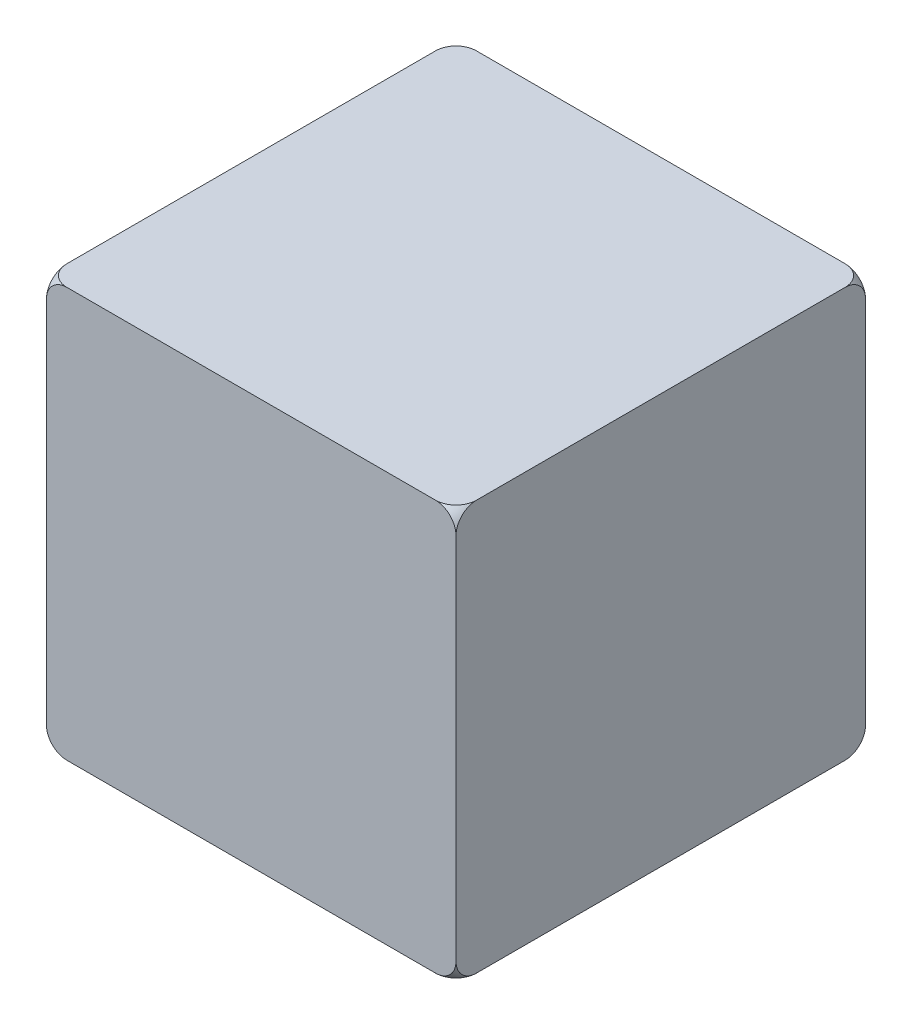
SolidWorks part; units mm, degrees
ref_plane "Plano frontal" through (0, 0, 0) normal (0, 0, 1) x (1, 0, 0)
ref_plane "Plano superior" through (0, 0, 0) normal (0, 1, 0) x (1, 0, 0)
ref_plane "Plano direito" through (0, 0, 0) normal (1, 0, 0) x (0, 0, -1)
sketch3d "3DSketch1"
  line L0 (0, 0, 0) -> (0.5, 0, 0) construction
  line L1 (0.5, 0, 0) -> (9.5, 0, 0) construction
  line L2 (9.5, 0, 0) -> (10, 0, 0) construction
  line L3 (10, 0, 0) -> (10, 0.5, 0) construction
  line L4 (10, 0.5, 0) -> (10, 9.5, 0) construction
  line L5 (10, 10, 0) -> (9.5, 10, 0) construction
  line L6 (9.5, 10, 0) -> (0.5, 10, 0) construction
  line L7 (0.5, 10, 0) -> (0, 10, 0) construction
  line L8 (0, 10, 0) -> (0, 9.5, 0) construction
  line L9 (0, 9.5, 0) -> (0, 0.5, 0) construction
  line L10 (0, 0.5, 0) -> (0, 0, 0) construction
  line L11 (10, 9.5, 0) -> (10, 10, 0) construction
  line L12 (0, 0, 0) -> (0, 0, 0.5) construction
  line L13 (0, 0, 0.5) -> (0, 0, 9.5) construction
  line L14 (0, 0, 9.5) -> (0, 0, 10) construction
  line L15 (0, 0, 10) -> (0, 0.5, 10) construction
  line L16 (0, 0.5, 10) -> (0, 9.5, 10) construction
  line L17 (0, 9.5, 10) -> (0, 10, 10) construction
  line L18 (0, 10, 0) -> (0, 10, 0.5) construction
  line L19 (0, 10, 0.5) -> (0, 10, 9.5) construction
  line L20 (0, 10, 9.5) -> (0, 10, 10) construction
  line L21 (0, 0, 10) -> (0.5, 0, 10) construction
  line L22 (0.5, 0, 10) -> (9.5, 0, 10) construction
  line L23 (9.5, 0, 10) -> (10, 0, 10) construction
  line L24 (10, 0, 0) -> (10, 0, 0.5) construction
  line L25 (10, 0, 0.5) -> (10, 0, 9.5) construction
  line L26 (10, 0, 9.5) -> (10, 0, 10) construction
  line L27 (10, 0, 10) -> (10, 0.5, 10) construction
  line L28 (10, 0.5, 10) -> (10, 9.5, 10) construction
  line L29 (10, 9.5, 10) -> (10, 10, 10) construction
  line L30 (10, 10, 0) -> (10, 10, 0.5) construction
  line L31 (10, 10, 0.5) -> (10, 10, 9.5) construction
  line L32 (10, 10, 9.5) -> (10, 10, 10) construction
  line L33 (0, 0, 0.5) -> (0.5, 0, 0.5) construction
  line L34 (0.5, 0, 0) -> (0.5, 0, 0.5) construction
  line L35 (0, 0, 0) -> (0.5, 0, 0.5) construction
  line L36 (0.5, 0, 0.5) -> (0.5, 0.5, 0.5) construction
  line L37 (0.5, 0, 10) -> (0.5, 0, 9.5) construction
  line L38 (9.5, 0, 10) -> (9.5, 0, 9.5) construction
  line L39 (9.5, 0, 0) -> (9.5, 0, 0.5) construction
  line L40 (0.5, 0, 9.5) -> (0.5, 0.5, 9.5) construction
  line L41 (9.5, 0, 9.5) -> (9.5, 0.5, 9.5) construction
  line L42 (9.5, 0, 0.5) -> (9.5, 0.5, 0.5) construction
  line L43 (0, 10, 9.5) -> (0.5, 10, 9.5) construction
  line L44 (0, 10, 0.5) -> (0.5, 10, 0.5) construction
  line L45 (10, 10, 0.5) -> (9.5, 10, 0.5) construction
  line L46 (10, 10, 9.5) -> (9.5, 10, 9.5) construction
  line L47 (0.5, 10, 9.5) -> (0.5, 9.5, 9.5) construction
  line L48 (0.5, 10, 0.5) -> (0.5, 9.5, 0.5) construction
  line L49 (9.5, 10, 0.5) -> (9.5, 9.5, 0.5) construction
  line L50 (9.5, 10, 9.5) -> (9.5, 9.5, 9.5) construction
  dimension "D1" = 0.5
  dimension "D2" = 10
sketch3d "3DSketch2"
  line L0 (0.5, 9.5, 0.5) -> (0, 9.5, 0.5) construction
  line L1 (0.5, 0.5, 0.5) -> (0, 0.5, 0.5) construction
  line L2 (0, 0.5, 0.5) -> (0, 1, 0.5) construction
  line L3 (0, 0, 0.5) -> (0.5, 0, 0.5) construction
  line L4 (0, 9.5, 0.5) -> (0, 9, 0.5) construction
  line L5 (0.5, 0, 0.5) -> (0.5, 0.5, 0.5) construction
  line L6 (0.5, -0.2071, 0.5) -> (0.5, 1.2071, 0.5)
  line L8 (0, 10, 0.5) -> (0.5, 10, 0.5) construction
  line L11 (0.5, 10, 0.5) -> (0.5, 9.5, 0.5) construction
  line L12 (0.5, -0.2071, 0.5) -> (0.5, 1.2071, 0.5)
  line L13 (0.5, 8.7929, 0.5) -> (0.5, 10.2071, 0.5)
  arc A0 (0.5, 1.2071, 0.5) -> (0.5, -0.2071, 0.5) centre (0.5, 0.5, 0.5) ccw
  arc A1 (0.5, 10.2071, 0.5) -> (0.5, 8.7929, 0.5) centre (0.5, 9.5, 0.5) ccw
  point P2 (0.5, 0.5, 1.2071)
  point P22 (0.5, 9.5, 1.2071)
ref_plane "Plano1" through (0, 0, 0.5) normal (0, 0, 1) x (1, 0, 0)
sketch "Esboço1" plane through (0, 0, 0.5) normal (0, 0, 1) x (1, 0, 0)
  line L0 (0.5, 8.7929) -> (0.5, 10.2071) construction
  line L1 (0.5, 8.7929) -> (0.5, 10.2071)
  line L2 (0.5, -0.2071) -> (0.5, 1.2071) construction
  line L3 (0.5, -0.2071) -> (0.5, 1.2071)
  arc A0 (0.5, 10.2071) -> (0.5, 8.7929) centre (0.5, 9.5) ccw construction
  arc A1 (0.5, 10.2071) -> (0.5, 8.7929) centre (0.5, 9.5) ccw
  arc A2 (0.5, 1.2071) -> (0.5, -0.2071) centre (0.5, 0.5) ccw construction
  arc A3 (0.5, 1.2071) -> (0.5, -0.2071) centre (0.5, 0.5) ccw
revolve "Revolução1" add sketch "Esboço1" angle 360 about L3
pattern_linear "Padrão linear1" count 2 spacing 9 along (1, 0, 0) of bodies 102 101
pattern_linear "Padrão linear2" count 2 spacing 9 along (0, 0, 1) of bodies 104 103 102 101
sketch "Esboço2" plane through (0, 0, 0) normal (0, 0, 1) x (1, 0, 0)
  line L1 (0, 0) -> (10, 0)
  line L2 (0, 0) -> (0, 10)
  line L3 (0, 10) -> (10, 10)
  line L4 (10, 0) -> (10, 10)
  line L5 (-5, -5) -> (15, -5)
  line L6 (-5, -5) -> (-5, 15)
  line L7 (-5, 15) -> (15, 15)
  line L8 (15, -5) -> (15, 15)
  dimension "D1" = 10
  dimension "D2" = 5
  dimension "D3" = 5
  dimension "D4" = 5
  dimension "D6" = 5
extrude "Corte-extrusão1" cut sketch "Esboço2" against normal through all and the other way through all
sketch "Esboço3" plane through (0, 0, 0) normal (1, 0, 0) x (0, 0, -1)
  line L1 (0, 0) -> (-10, 0)
  line L2 (0, 0) -> (0, 10)
  line L3 (0, 10) -> (-10, 10)
  line L4 (-10, 0) -> (-10, 10)
  line L5 (-15, 15) -> (5, 15)
  line L6 (-15, 15) -> (-15, -5)
  line L7 (-15, -5) -> (5, -5)
  line L8 (5, 15) -> (5, -5)
  dimension "D1" = 10
  dimension "D2" = 5
  dimension "D3" = 5
  dimension "D4" = 5
  dimension "D5" = 5
extrude "Corte-extrusão4" cut sketch "Esboço3" against normal blind 10 and the other way blind 17
sketch "Esboço4" plane through (0, 0, 0.5) normal (0, 0, 1) x (1, 0, 0)
  line L1 (0, 10) -> (10, 10)
  line L2 (0, 10) -> (0, 0)
  line L3 (0, 0) -> (10, 0)
  line L4 (10, 10) -> (10, 0)
extrude "Ressalto-extrusão1" add sketch "Esboço4" along normal up to vertex (9 mm away) up to point (0, 10, 9.5)
ref_plane "Plano2" through (0.5, 0, 0) normal (-1, 0, 0) x (0, 0, 1)
sketch "Esboço5" plane through (0.5, 0, 0) normal (-1, 0, 0) x (0, 0, 1)
  line L1 (0, 10) -> (10, 10)
  line L2 (0, 10) -> (0, 0)
  line L3 (0, 0) -> (10, 0)
  line L4 (10, 10) -> (10, 0)
extrude "Ressalto-extrusão2" add sketch "Esboço5" against normal up to vertex (9 mm away) up to point (9.5, 10, 10)
ref_plane "Plano3" through (0, 0.5, 0) normal (0, 1, 0) x (1, 0, 0)
sketch "Esboço6" plane through (0, 0.5, 0) normal (0, 1, 0) x (1, 0, 0)
  line L1 (0, 0) -> (10, 0)
  line L2 (0, 0) -> (0, -10)
  line L3 (0, -10) -> (10, -10)
  line L4 (10, 0) -> (10, -10)
extrude "Ressalto-extrusão3" add sketch "Esboço6" along normal up to vertex (9 mm away) up to point (10, 9.5, 10)
